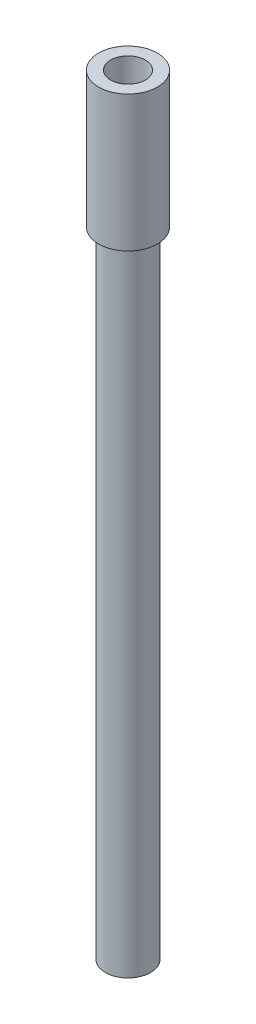
SolidWorks part; units mm, degrees
ref_plane "Front Plane" through (0, 0, 0) normal (0, 0, 1) x (1, 0, 0)
ref_plane "Top Plane" through (0, 0, 0) normal (0, 1, 0) x (1, 0, 0)
ref_plane "Right Plane" through (0, 0, 0) normal (1, 0, 0) x (0, 0, -1)
sketch "Sketch3" plane through (0, 0, 0) normal (0, 1, 0) x (1, 0, 0)
  circle A0 centre (0, 0) radius 2.5
  dimension "D1" = 5
extrude "Boss-Extrude2" add sketch "Sketch3" along normal blind 70
sketch "Sketch4" plane through (0, 70, 0) normal (0, 1, 0) x (1, 0, 0)
  circle A0 centre (0, 0) radius 3.25
  dimension "D1" = 6.5
extrude "Boss-Extrude3" add sketch "Sketch4" along normal blind 15
sketch "Sketch5" plane through (0, 85, 0) normal (0, 1, 0) x (1, 0, 0)
  circle A0 centre (0, 0) radius 1.9188
extrude "Cut-Extrude1" cut sketch "Sketch5" against normal blind 5
